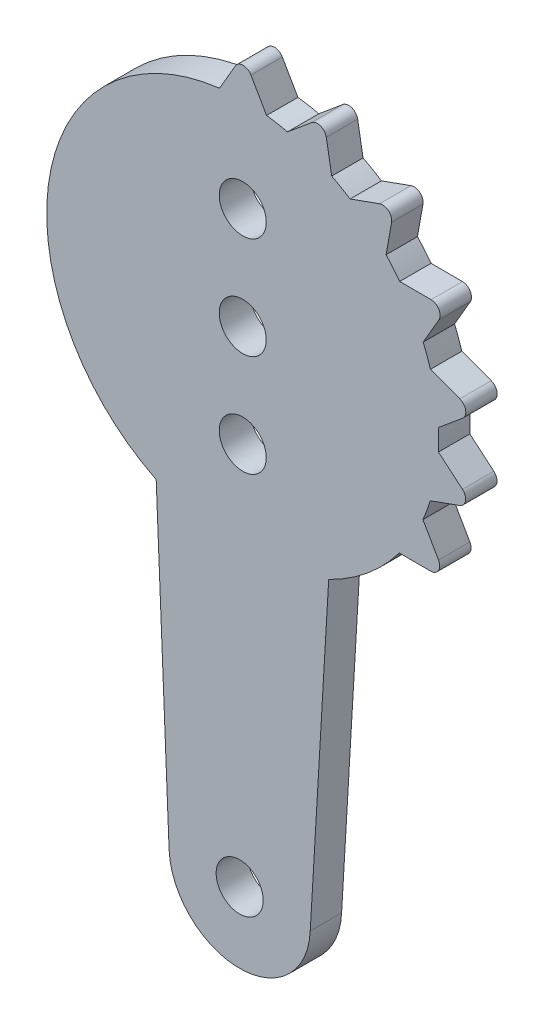
SolidWorks part; units mm, degrees
ref_plane "Front Plane" through (0, 0, 0) normal (0, 0, 1) x (1, 0, 0)
ref_plane "Top Plane" through (0, 0, 0) normal (0, 1, 0) x (1, 0, 0)
ref_plane "Right Plane" through (0, 0, 0) normal (1, 0, 0) x (0, 0, -1)
sketch "Sketch1" plane through (0, 0, 0) normal (0, 0, 1) x (1, 0, 0)
  line L0 (-5.3228, 19.8328) -> (-4.5, -0.185)
  line L1 (5.6772, 19.8147) -> (4.5, -0.1853)
  line L2 (4.5859, 44.5001) -> (3.0506, 43.2183)
  line L3 (0.7204, 45.1904) -> (1.7162, 43.4559)
  line L4 (-0.2796, 45.1904) -> (-1.2838, 43.4608)
  line L5 (5.5255, 44.158) -> (5.868, 42.1876)
  line L6 (8.9217, 42.1873) -> (7.0407, 41.5079)
  line L7 (9.6878, 41.5445) -> (9.3356, 39.5758)
  line L8 (12.2051, 38.5311) -> (10.2051, 38.536)
  line L9 (12.7051, 37.665) -> (11.7008, 35.9355)
  line L10 (14.04, 33.9723) -> (12.1623, 34.661)
  line L11 (14.2136, 32.9875) -> (12.6784, 31.7058)
  line L12 (14.205, 29.061) -> (12.6761, 30.3504)
  line L13 (14.0314, 28.0762) -> (12.1503, 27.3968)
  line L14 (12.6803, 24.3894) -> (11.6846, 26.1239)
  line L15 (12.1803, 23.5233) -> (10.1803, 23.5283)
  line L16 (0.1956, 31.0487) -> (0.1956, 37.5487) construction
  line L17 (0.1956, 31.0487) -> (0.1956, 24.5487) construction
  arc A0 (-5.3228, 19.8328) -> (-1.2838, 43.4608) centre (0.1956, 31.0487) cw
  arc A1 (-4.5, -0.185) -> (4.5, -0.1853) centre (0, 0) ccw
  circle A2 centre (0.1956, 31.0487) radius 1.5
  circle A3 centre (0.1956, 37.5487) radius 1.5
  circle A4 centre (0.1956, 24.5487) radius 1.5
  circle A5 centre (0, 0) radius 1.5
  arc A6 (-0.2796, 45.1904) -> (0.7204, 45.1904) centre (0.2204, 44.9001) cw
  arc A7 (1.7162, 43.4559) -> (3.0506, 43.2183) centre (0.1956, 31.0487) cw
  arc A8 (4.5859, 44.5001) -> (5.5255, 44.158) centre (4.9564, 44.0562) cw
  arc A9 (8.9217, 42.1873) -> (9.6878, 41.5445) centre (9.1181, 41.6435) cw
  arc A10 (12.2051, 38.5311) -> (12.7051, 37.665) centre (12.2037, 37.9529) cw
  arc A11 (14.04, 33.9723) -> (14.2136, 32.9875) centre (13.8409, 33.4295) cw
  arc A12 (14.205, 29.061) -> (14.0314, 28.0762) centre (13.8323, 28.619) cw
  arc A13 (12.6803, 24.3894) -> (12.1803, 23.5233) centre (12.1789, 24.1015) cw
  arc A14 (9.3356, 39.5758) -> (10.2051, 38.536) centre (0.1956, 31.0487) cw
  arc A15 (5.868, 42.1876) -> (7.0407, 41.5079) centre (0.1956, 31.0487) cw
  arc A16 (11.7008, 35.9355) -> (12.1623, 34.661) centre (0.1956, 31.0487) cw
  arc A17 (12.6784, 31.7058) -> (12.6761, 30.3504) centre (0.1956, 31.0487) cw
  arc A18 (12.1503, 27.3968) -> (11.6846, 26.1239) centre (0.1956, 31.0487) cw
  arc A19 (10.1803, 23.5283) -> (5.6772, 19.8147) centre (0.1956, 31.0487) cw
  point P50 (0.1956, 31.0487)
  dimension "D2" = 3
  dimension "D3" = 12.5
  dimension "D6" = 9
  dimension "D8" = 4.5038
  dimension "D11" = 3
  dimension "D5" = 6.5
  dimension "D4" = 6.5
  dimension "D7" = 11
  dimension "D9" = 20
  dimension "D10" = 31.0487
  dimension "D12" = 44.9001
  dimension "D13" = 7
  dimension "D14" = 2
  dimension "D15" = 2
  dimension "D16" = 1
extrude "Boss-Extrude1" add sketch "Sketch1" along normal blind 2
ref_axis "Axis1" through (0.1956, 31.0487, 2) along (0, 0, -1)
